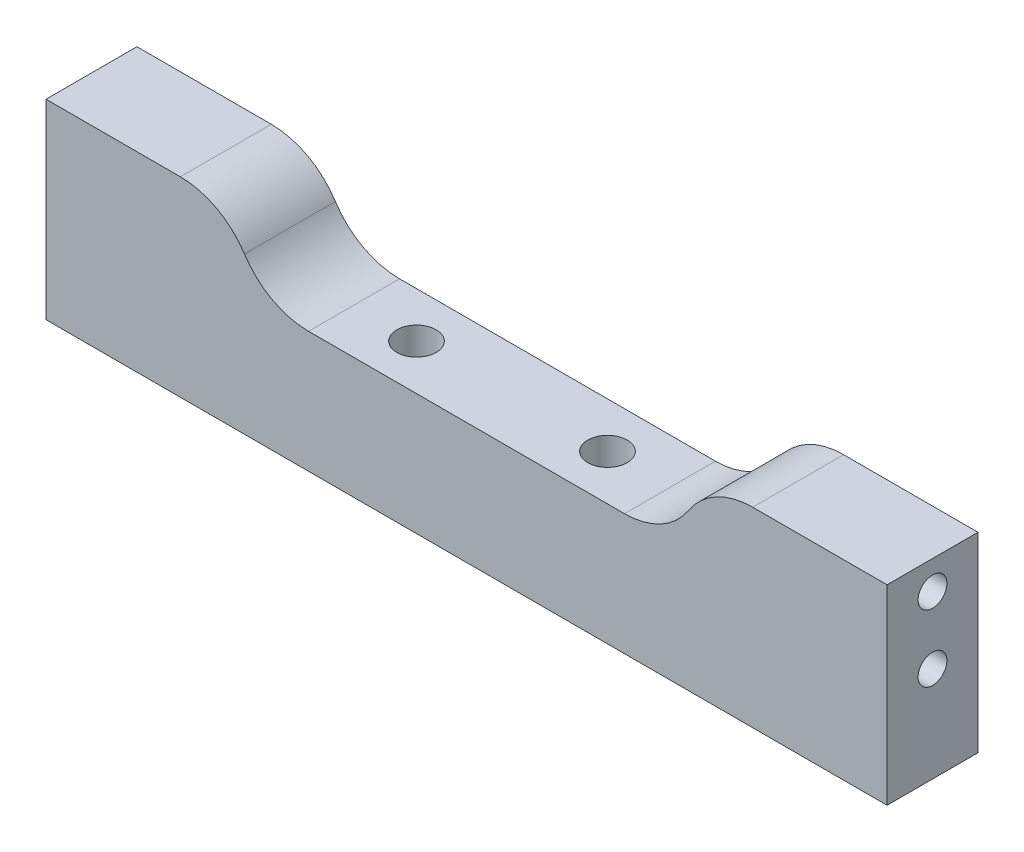
SolidWorks part; units mm, degrees
ref_plane "Front Plane" through (0, 0, 0) normal (0, 0, 1) x (1, 0, 0)
ref_plane "Top Plane" through (0, 0, 0) normal (0, 1, 0) x (1, 0, 0)
ref_plane "Right Plane" through (0, 0, 0) normal (1, 0, 0) x (0, 0, -1)
sketch "Sketch1" plane through (0, 0, 0) normal (0, 0, 1) x (1, 0, 0)
  line L1 (-22.02, -5) -> (22.02, -5)
  line L2 (-22.02, -5) -> (-22.02, 5)
  line L3 (-22.02, 5) -> (22.02, 5)
  line L4 (22.02, -5) -> (22.02, 5)
  line L5 (-22.02, -5) -> (22.02, 5) construction
  line L6 (-22.02, 5) -> (22.02, -5) construction
  point P0 (0, 0)
  dimension "D1" = 10
  dimension "D2" = 44.04
extrude "Boss-Extrude1" add sketch "Sketch1" along normal blind 4.7625
sketch "Sketch2" plane through (0, 5, 0) normal (0, 1, 0) x (1, 0, 0)
  line L0 (-22.02, -2.3813) -> (22.02, -2.3813) construction
  line L1 (-22.02, -4.7625) -> (-22.02, 0) construction
  line L2 (22.02, -4.7625) -> (22.02, 0) construction
  line L4 (22.02, 0) -> (-22.02, 0) construction
  line L5 (0, -4.7625) -> (0, 0) construction
  line L6 (22.02, -4.7625) -> (-22.02, -4.7625) construction
  circle A0 centre (-5, -2.3813) radius 1.03
  circle A1 centre (5, -2.3813) radius 1.03
  dimension "D1" = 2.06
  dimension "D2" = 2.06
  dimension "D3" = 5
  dimension "D4" = 5
extrude "Cut-Extrude1" cut sketch "Sketch2" against normal through all
ref_plane "Plane1" through (0, 0, 2.3813) normal (0, 0, -1) x (-1, 0, 0)
hole_wizard "#1-64 Tapped Hole1" positions "Sketch4" profile "Sketch3" tap size "#1-64" standard "ANSI Inch"
sketch "Sketch4" plane through (-22.02, 0, 0) normal (-1, 0, 0) x (0, 0, 1)
  line L4 (4.7625, 5) -> (0, 5) construction
  point P0 (2.3813, 3.5)
  point P2 (2.3813, 0)
  dimension "D1" = 1.5
  dimension "D2" = 5
sketch "Sketch3" plane through (-22.02, 3.5, 2.3813) normal (0, 1, 0) x (0, 0, 1)
  line L0 (0, 0) -> (0, 6.804)
  line L1 (0, 6.804) -> (0.7556, 6.35)
  line L2 (0.7556, 6.35) -> (0.7556, 0)
  line L5 (0.7556, 0) -> (0, 0)
  line L10 (0, 6.804) -> (-0.7557, 6.35) construction
  line L11 (0, -6.35) -> (0, 107.95) construction
  dimension "Tap Drill Dia." = 1.5113
  dimension "Tap Drill Depth" = 6.35
  dimension "Drill Angle" = 118
cosmetic thread "Hole Thread1" parameters "D1"=6.34, "D2"=1.8542
cosmetic thread "Hole Thread2" parameters "D1"=6.34, "D2"=1.8542
hole_wizard "#1-64 Tapped Hole2" positions "Sketch6" profile "Sketch5" tap size "#1-64" standard "ANSI Inch"
sketch "Sketch6" plane through (22.02, 0, 0) normal (1, 0, 0) x (0, 0, -1)
  line L4 (-4.7625, 5) -> (0, 5) construction
  point P0 (-2.3813, 3.5)
  point P2 (-2.3813, 0)
  dimension "D1" = 1.5
  dimension "D2" = 5
sketch "Sketch5" plane through (22.02, 3.5, 2.3813) normal (0, 1, 0) x (0, 0, -1)
  line L0 (0, 0) -> (0, 6.804)
  line L1 (0, 6.804) -> (0.7556, 6.35)
  line L2 (0.7556, 6.35) -> (0.7556, 0)
  line L5 (0.7556, 0) -> (0, 0)
  line L10 (0, 6.804) -> (-0.7557, 6.35) construction
  line L11 (0, -6.35) -> (0, 107.95) construction
  dimension "Tap Drill Dia." = 1.5113
  dimension "Tap Drill Depth" = 6.35
  dimension "Drill Angle" = 118
cosmetic thread "Hole Thread3" parameters "D1"=6.34, "D2"=1.8542
cosmetic thread "Hole Thread4" parameters "D1"=6.34, "D2"=1.8542
sketch "Sketch7" plane through (0, 0, 4.7625) normal (0, 0, 1) x (1, 0, 0)
  line L0 (22.02, 5) -> (-22.02, 5) construction
  line L1 (-11, 5) -> (11, 5)
  line L2 (-11, 5) -> (-11, 1.35)
  line L3 (-11, 1.35) -> (11, 1.35)
  line L4 (11, 5) -> (11, 1.35)
  line L5 (-22.02, -5) -> (22.02, -5) construction
  line L6 (0, 0) -> (0, 5) construction
  point P11 (0, 1.35)
  dimension "D1" = 6.35
  dimension "D2" = 22
extrude "Cut-Extrude2" cut sketch "Sketch7" against normal blind 10
fillet "Fillet1" radius 4 2 edges at (11, 5, 2.3813) (-11, 5, 2.3813)
fillet "Fillet2" radius 4 2 edges at (11, 1.35, 2.3813) (-11, 1.35, 2.3813)
